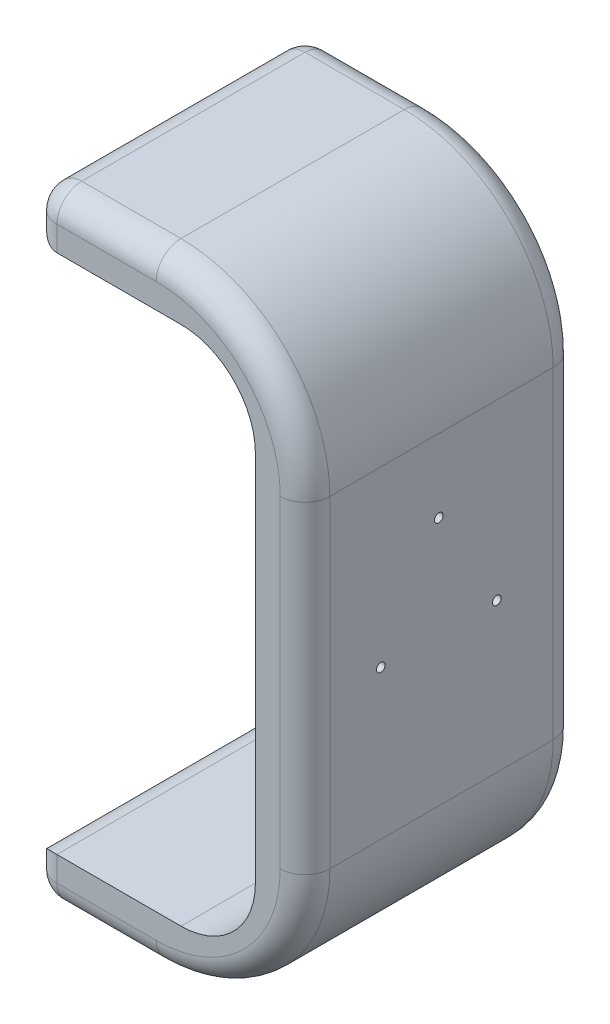
SolidWorks part; units mm, degrees
ref_plane "Front Plane" through (0, 0, 0) normal (0, 0, 1) x (1, 0, 0)
ref_plane "Top Plane" through (0, 0, 0) normal (0, 1, 0) x (1, 0, 0)
ref_plane "Right Plane" through (0, 0, 0) normal (1, 0, 0) x (0, 0, -1)
sketch "Sketch1" plane through (0, 0, 0) normal (0, 0, 1) x (1, 0, 0)
  line L0 (0, 0) -> (110, 0)
  line L1 (110, 0) -> (110, -250)
  line L2 (110, -250) -> (0, -250)
  line L3 (0, -250) -> (0, -230)
  line L4 (0, -230) -> (90, -230)
  line L5 (90, -230) -> (90, -20)
  line L6 (90, -20) -> (0, -20)
  line L7 (0, -20) -> (0, 0)
  dimension "D1" = 20
  dimension "D2" = 20
  dimension "D3" = 250
  dimension "D4" = 110
  dimension "D5" = 90
extrude "Boss-Extrude1" add sketch "Sketch1" along normal blind 110
fillet "Fillet1" radius 60 2 edges at (110, 0, 55) (110, -250, 55)
fillet "Fillet3" radius 30 2 edges at (90, -20, 55) (90, -230, 55)
fillet "Fillet4" radius 10 18 edges at (25, -250, 0) (92.4264, -232.4264, 0) (25, 0, 0) (92.4264, -17.5736, 0) (25, -250, 110) (92.4264, -232.4264, 110) (25, 0, 110) (92.4264, -17.5736, 110) (0, -240, 0) (0, -240, 110) (0, -10, 0) (0, -10, 110) (0, -20, 55) (0, 0, 55) (0, -230, 55) (0, -250, 55) (110, -125, 0) (110, -125, 110)
sketch "Sketch2" plane through (90, 0, 0) normal (-1, 0, 0) x (0, 0, 1)
  circle A0 centre (56.0696, -116.4409) radius 27 construction
  circle A1 centre (56.0696, -89.4409) radius 1.75
  circle A2 centre (79.4523, -129.9409) radius 1.75
  circle A3 centre (32.6869, -129.9409) radius 1.75
  point P11 (56.0696, -116.4409)
  dimension "D1" = 54
  dimension "D2" = 3.5
  dimension "D3" = 3
extrude "Cut-Extrude1" cut sketch "Sketch2" against normal blind 250
sketch "Sketch4" plane through (0, -230, 0) normal (0, 1, 0) x (1, 0, 0)
